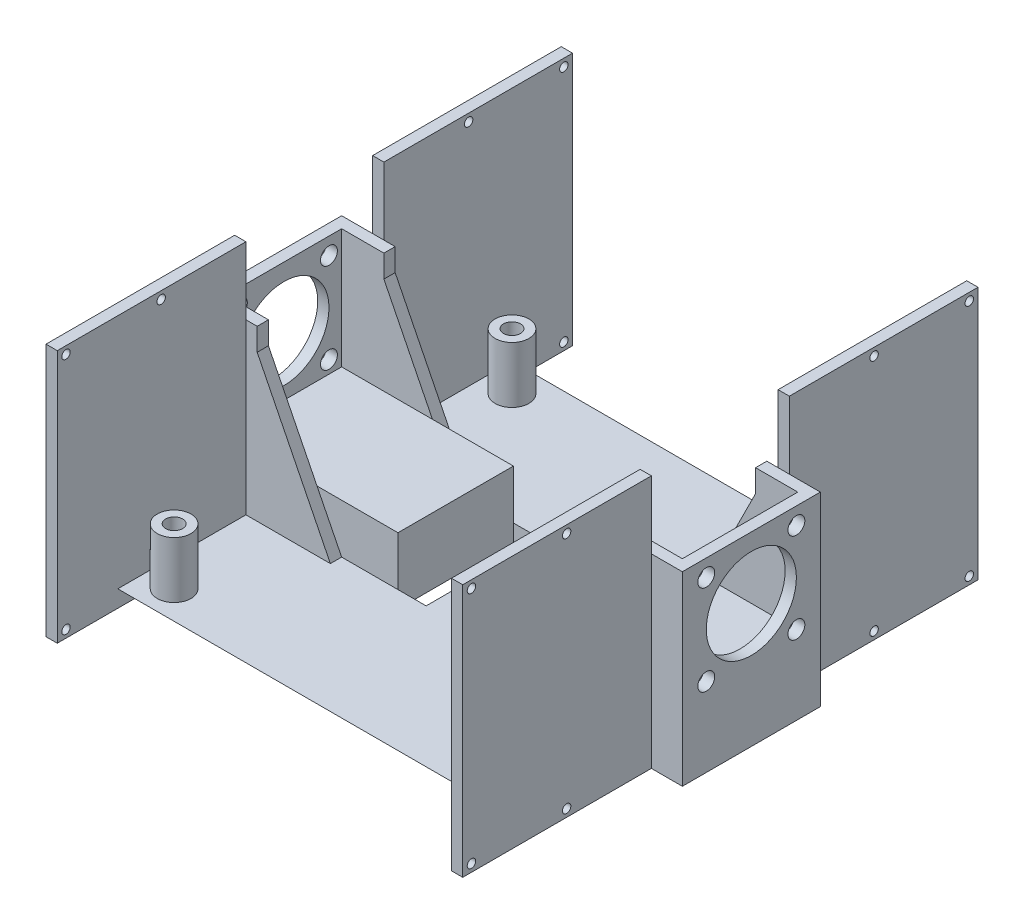
SolidWorks part; units mm, degrees
ref_plane "Front Plane" through (0, 0, 0) normal (0, 0, 1) x (1, 0, 0)
ref_plane "Top Plane" through (0, 0, 0) normal (0, 1, 0) x (1, 0, 0)
ref_plane "Right Plane" through (0, 0, 0) normal (1, 0, 0) x (0, 0, -1)
sketch "Sketch1" plane through (0, 0, 0) normal (0, 1, 0) x (1, 0, 0)
  line L1 (0, 0) -> (70, 0)
  line L2 (0, 0) -> (0, 70)
  line L3 (0, 70) -> (70, 70)
  line L4 (70, 0) -> (70, 70)
  dimension "D1" = 70
extrude "Boss-Extrude1" add sketch "Sketch1" along normal blind 3
sketch "Sketch2" plane through (0, 3, 0) normal (0, 1, 0) x (1, 0, 0)
  line L0 (0, 70) -> (0, 0) construction
  line L1 (0, 24.75) -> (-7.5, 24.75)
  line L2 (0, 24.75) -> (0, 45.25)
  line L3 (0, 45.25) -> (-7.5, 45.25)
  line L4 (-7.5, 24.75) -> (-7.5, 45.25)
  line L5 (70, 0) -> (70, 70) construction
  line L6 (70, 24.75) -> (77.5, 24.75)
  line L7 (70, 24.75) -> (70, 45.25)
  line L8 (70, 45.25) -> (77.5, 45.25)
  line L9 (77.5, 24.75) -> (77.5, 45.25)
  line L10 (-7.5, 45.25) -> (7.5, 45.25) construction
  line L11 (77.5, 45.25) -> (62.5, 45.25) construction
  point P13 (70, 35)
  point P14 (70, 35)
  point P15 (0, 35)
  point P16 (0, 35)
  dimension "D1" = 15
  dimension "D2" = 55
  dimension "D3" = 20.5
extrude "Boss-Extrude2" add sketch "Sketch2" against normal up to surface (3 mm away) up to face at (35, 0, -35)
sketch "Sketch3" plane through (0, 3, 0) normal (0, 1, 0) x (1, 0, 0)
  line L0 (-7.5, 24.75) -> (0, 24.75) construction
  line L1 (-7.5, 45.25) -> (-5.5, 45.25)
  line L2 (-7.5, 45.25) -> (-7.5, 24.75)
  line L3 (-7.5, 24.75) -> (-5.5, 24.75)
  line L4 (-5.5, 45.25) -> (-5.5, 24.75)
  line L5 (77.5, 45.25) -> (70, 45.25) construction
  line L6 (77.5, 24.75) -> (75.5, 24.75)
  line L7 (77.5, 24.75) -> (77.5, 45.25)
  line L8 (77.5, 45.25) -> (75.5, 45.25)
  line L9 (75.5, 24.75) -> (75.5, 45.25)
  dimension "D1" = 2
extrude "Boss-Extrude3" add sketch "Sketch3" along normal blind 30
sketch "Sketch4" plane through (-5.5, 0, 0) normal (1, 0, 0) x (0, 0, -1)
  line L0 (24.75, 12) -> (45.25, 12) construction
  line L1 (24.75, 33) -> (24.75, 3) construction
  line L2 (45.25, 33) -> (45.25, 3) construction
  line L5 (24.75, 33) -> (45.25, 33) construction
  line L6 (27, 14) -> (43, 14) construction
  line L7 (43, 14) -> (43, 30) construction
  circle A0 centre (35, 22) radius 8
  circle A1 centre (43, 30) radius 1.5
  circle A2 centre (43, 14) radius 1.5
  circle A3 centre (27, 30) radius 1.5
  circle A4 centre (27, 14) radius 1.5
  point P13 (35, 33)
  point P21 (43, 22)
  point P23 (35, 14)
  point P24 (35, 12)
  dimension "D2" = 16
  dimension "D7" = 3
  dimension "D1" = 9
  dimension "D3" = 10
  dimension "D4" = 16
  dimension "D5" = 16
  dimension "D6" = 10
extrude "Cut-Extrude1" cut sketch "Sketch4" against normal through all both and the other way through all
sketch "Sketch5" plane through (0, 3, 0) normal (0, 1, 0) x (1, 0, 0)
  line L0 (-7.5, 45.25) -> (-7.5, 24.75) construction
  line L1 (2, 24.75) -> (-7.5, 24.75)
  line L2 (2, 24.75) -> (2, 22.75)
  line L3 (2, 22.75) -> (-7.5, 22.75)
  line L4 (-7.5, 24.75) -> (-7.5, 22.75)
  line L5 (-5.5, 35) -> (77.5, 35) construction
  line L6 (-5.5, 24.75) -> (-5.5, 45.25) construction
  line L7 (77.5, 24.75) -> (77.5, 45.25) construction
  line L8 (77.5, 24.75) -> (77.5, 45.25)
  line L9 (35, 0) -> (35, 70) construction
  line L10 (0, 0) -> (70, 0) construction
  line L11 (70, 70) -> (0, 70) construction
  line L12 (2, 47.25) -> (-7.5, 47.25)
  line L13 (-7.5, 45.25) -> (-7.5, 47.25)
  line L14 (2, 45.25) -> (-7.5, 45.25)
  line L15 (2, 45.25) -> (2, 47.25)
  line L16 (68, 22.75) -> (77.5, 22.75)
  line L17 (77.5, 24.75) -> (77.5, 22.75)
  line L18 (68, 24.75) -> (77.5, 24.75)
  line L19 (68, 24.75) -> (68, 22.75)
  line L20 (68, 45.25) -> (68, 47.25)
  line L21 (68, 45.25) -> (77.5, 45.25)
  line L22 (77.5, 45.25) -> (77.5, 47.25)
  line L23 (68, 47.25) -> (77.5, 47.25)
  line L24 (-5.5, 24.75) -> (0, 24.75) construction
  dimension "D1" = 2
  dimension "D2" = 2
extrude "Boss-Extrude4" add sketch "Sketch5" against normal up to surface and the other way up to surface contours L12 L13 L14 L15 | L2 L1 L4 L3 | L20 L23 L22 L21 | L16 L17 L18 L19 up to face at (35, 0, -35) other way up to face at (76.5, 33, -35)
sketch "Sketch6" plane through (0, 0, -47.25) normal (0, 0, -1) x (-1, 0, 0)
  line L0 (-70, 33) -> (-55, 3)
  line L2 (-55, 3) -> (-70, 3)
  line L3 (-70, 3) -> (-70, 33)
  line L4 (0, 33) -> (-15, 3)
  line L5 (-15, 3) -> (0, 3)
  line L6 (0, 3) -> (0, 33)
  line L7 (-68, 33) -> (-77.5, 33) construction
  line L8 (-2, 33) -> (7.5, 33) construction
  dimension "D1" = 15
extrude "Boss-Extrude5" add sketch "Sketch6" against normal up to surface (24.5 mm away) up to face at (71.8333, 12, -22.75)
sketch "Sketch7" plane through (0, 3, 0) normal (0, 1, 0) x (1, 0, 0)
  line L1 (75.5, 24.75) -> (-5.5, 24.75)
  line L2 (75.5, 24.75) -> (75.5, 45.25)
  line L3 (75.5, 45.25) -> (-5.5, 45.25)
  line L4 (-5.5, 24.75) -> (-5.5, 45.25)
extrude "Cut-Extrude2" cut sketch "Sketch7" along normal through all
sketch "Sketch8" plane through (0, 3, 0) normal (0, 1, 0) x (1, 0, 0)
  line L0 (15, 45.25) -> (-5.5, 45.25) construction
  line L1 (25, 45.25) -> (30, 45.25)
  line L2 (25, 45.25) -> (25, 24.75)
  line L3 (25, 24.75) -> (30, 24.75)
  line L4 (30, 45.25) -> (30, 24.75)
  line L5 (40, 45.25) -> (45, 45.25)
  line L6 (40, 45.25) -> (40, 24.75)
  line L7 (40, 24.75) -> (45, 24.75)
  line L8 (45, 45.25) -> (45, 24.75)
  line L9 (-5.5, 24.75) -> (15, 24.75) construction
  line L10 (25, 45.25) -> (15, 45.25) construction
  line L11 (45, 45.25) -> (55, 45.25) construction
  line L12 (-5.5, 24.75) -> (-5.5, 45.25) construction
  dimension "D1" = 30.5
  dimension "D2" = 5
extrude "Cut-Extrude3" cut sketch "Sketch8" against normal through all
sketch "Sketch17" plane through (75.5, 0, 0) normal (-1, 0, 0) x (0, 0, 1)
  line L0 (-45.25, 33) -> (-45.25, 3) construction
  line L1 (-24.75, 3) -> (-45.25, 3)
  line L2 (-24.75, 3) -> (-24.75, 11.75)
  line L3 (-24.75, 11.75) -> (-45.25, 11.75)
  line L4 (-45.25, 3) -> (-45.25, 11.75)
  circle A0 centre (-27, 14) radius 1.5 construction
  circle A1 centre (-27, 14) radius 1.5
  line M6 (-45.25, 3) -> (-24.75, 3)
  line M7 (-24.75, 3) -> (-24.75, 33)
  line M9 (-45.25, 33) -> (-45.25, 3)
  dimension "D1" = 2.25
extrude "Boss-Extrude7" add sketch "Sketch17" along normal up to surface (30.5 mm away) contours L3 M7 M9 M6 region at (75.5, 7.375, -35) up to face at (45, 1.5, -35)
sketch "Sketch18" plane through (-5.5, 0, 0) normal (1, 0, 0) x (0, 0, -1)
  line L6 (24.75, 3) -> (24.75, 0)
  line L7 (24.75, 11.75) -> (24.75, 3)
  line L8 (45.25, 11.75) -> (24.75, 11.75)
  line L9 (45.25, 3) -> (45.25, 11.75)
  line L10 (45.25, 0) -> (45.25, 3)
  line L11 (24.75, 0) -> (45.25, 0)
  line L12 (24.75, 3) -> (24.75, 0)
  line L13 (24.75, 11.75) -> (24.75, 3)
  line L14 (45.25, 11.75) -> (24.75, 11.75)
  line L15 (45.25, 3) -> (45.25, 11.75)
  line L16 (45.25, 0) -> (45.25, 3)
  line L17 (24.75, 0) -> (45.25, 0)
  dimension "D1" = 0
extrude "Boss-Extrude8" add sketch "Sketch18" along normal up to surface (30.5 mm away) up to face at (25, 1.5, -35)
sketch "Sketch19" plane through (0, 3, 0) normal (0, 1, 0) x (1, 0, 0)
  line L0 (65, 5) -> (65, 65) construction
  line L1 (65, 65) -> (5, 65) construction
  line L2 (5, 65) -> (5, 5) construction
  line L3 (5, 5) -> (65, 5) construction
  line L4 (0, 70) -> (0, 47.25) construction
  line L5 (70, 70) -> (0, 70) construction
  line L6 (70, 0) -> (70, 22.75) construction
  line L7 (0, 0) -> (70, 0) construction
  circle A0 centre (5, 5) radius 3
  circle A1 centre (65, 5) radius 3
  circle A2 centre (65, 65) radius 3
  circle A3 centre (5, 65) radius 3
  dimension "D5" = 6
  dimension "D1" = 5
  dimension "D2" = 5
  dimension "D3" = 5
  dimension "D4" = 5
extrude "Boss-Extrude9" add sketch "Sketch19" along normal blind 10
sketch "Sketch20" plane through (0, 13, 0) normal (0, 1, 0) x (1, 0, 0)
  circle A0 centre (5, 65) radius 1.5
  circle A1 centre (65, 65) radius 1.5
  circle A2 centre (65, 5) radius 1.5
  circle A3 centre (5, 5) radius 1.5
  dimension "D1" = 3
extrude "Cut-Extrude4" cut sketch "Sketch20" against normal through all
fillet "Fillet1" radius 10 2 edges at (35, 0, 0) (35, 0, -70)
sketch "Sketch27" plane through (0, 0, -22.75) normal (0, 0, 1) x (1, 0, 0)
  line L0 (70, 0) -> (72, 0)
  line L1 (70, 0) -> (77.5, 0) construction
  line L2 (70, 0) -> (70, 45)
  line L3 (72, 0) -> (72, 45)
  line L4 (72, 45) -> (70, 45)
  dimension "D1" = 45
  dimension "2" = 2
extrude "Boss-Extrude14" add sketch "Sketch27" along normal blind 33.5
sketch "Sketch28" plane through (0, 0, -47.25) normal (0, 0, -1) x (-1, 0, 0)
  line L0 (-70, 0) -> (-72, 0)
  line L1 (-72, 0) -> (-72, 45)
  line L2 (-70, 0) -> (-70, 45)
  line L3 (-70, 45) -> (-72, 45)
  line L4 (0, 0) -> (2, 0)
  line L5 (0, 0) -> (7.5, 0) construction
  line L6 (2, 0) -> (2, 45)
  line L7 (2, 45) -> (0, 45)
  line L8 (0, 45) -> (0, 0)
  dimension "D1" = 2
  dimension "D2" = 45
  dimension "D3" = 2
  dimension "D4" = 45
extrude "Boss-Extrude15" add sketch "Sketch28" along normal blind 33.5
sketch "Sketch29" plane through (0, 0, -22.75) normal (0, 0, 1) x (1, 0, 0)
  line L1 (0, 0) -> (-2, 0)
  line L2 (0, 0) -> (0, 45)
  line L3 (0, 45) -> (-2, 45)
  line L4 (-2, 0) -> (-2, 45)
  dimension "D1" = 2
  dimension "D2" = 45
extrude "Boss-Extrude16" add sketch "Sketch29" along normal blind 33.5
sketch "Sketch30" plane through (72, 0, 0) normal (1, 0, 0) x (0, 0, -1)
  line L0 (-10.75, 45) -> (-9.2, 45)
  line L1 (-10.75, 45) -> (22.75, 45) construction
  line L2 (-9.2, 45) -> (-9.2, 43.65)
  line L3 (-9.2, 43.65) -> (-9.95, 43.65)
  circle A0 centre (-9.2, 43.65) radius 0.75
  dimension "D1" = 1.55
  dimension "D2" = 1.35
  dimension "D3" = 0.75
sketch "Sketch31" plane through (72, 0, 0) normal (1, 0, 0) x (0, 0, -1)
  line L0 (-10.75, 45) -> (-9.2, 45) construction
  line L1 (-9.2, 45) -> (-9.2, 43.65) construction
  line L2 (-9.2, 43.65) -> (-9.95, 43.65) construction
  line L3 (-10.75, 45) -> (9.25, 45) construction
  line L4 (-10.75, 45) -> (22.75, 45) construction
  line L5 (9.25, 45) -> (9.25, 43.65) construction
  line L6 (9.25, 43.65) -> (7.7, 43.65) construction
  line L7 (7.7, 43.65) -> (7.7, 42.9)
  line L8 (-10.75, 22.5) -> (22.0229, 22.5) construction
  line L9 (-10.75, 0) -> (-10.75, 45) construction
  line L10 (-10.75, 0) -> (80.75, 0) construction
  line L11 (35, 0) -> (35, 45) construction
  circle A0 centre (-9.2, 43.65) radius 0.75
  circle A1 centre (7.7, 43.65) radius 0.75
  circle A2 centre (7.7, 1.35) radius 0.75
  circle A3 centre (-9.2, 1.35) radius 0.75
  circle A4 centre (62.3, 1.35) radius 0.75
  circle A5 centre (79.2, 1.35) radius 0.75
  circle A6 centre (79.2, 43.65) radius 0.75
  circle A7 centre (62.3, 43.65) radius 0.75
  point P38 (0, 0)
  dimension "D1" = 0.75
  dimension "20" = 20
  dimension "1.55" = 1.55
extrude "Cut-Extrude6" cut sketch "Sketch31" against normal through all contours A1 | A0 | A3 | A2 | A5 | A4 | A7 | A6
